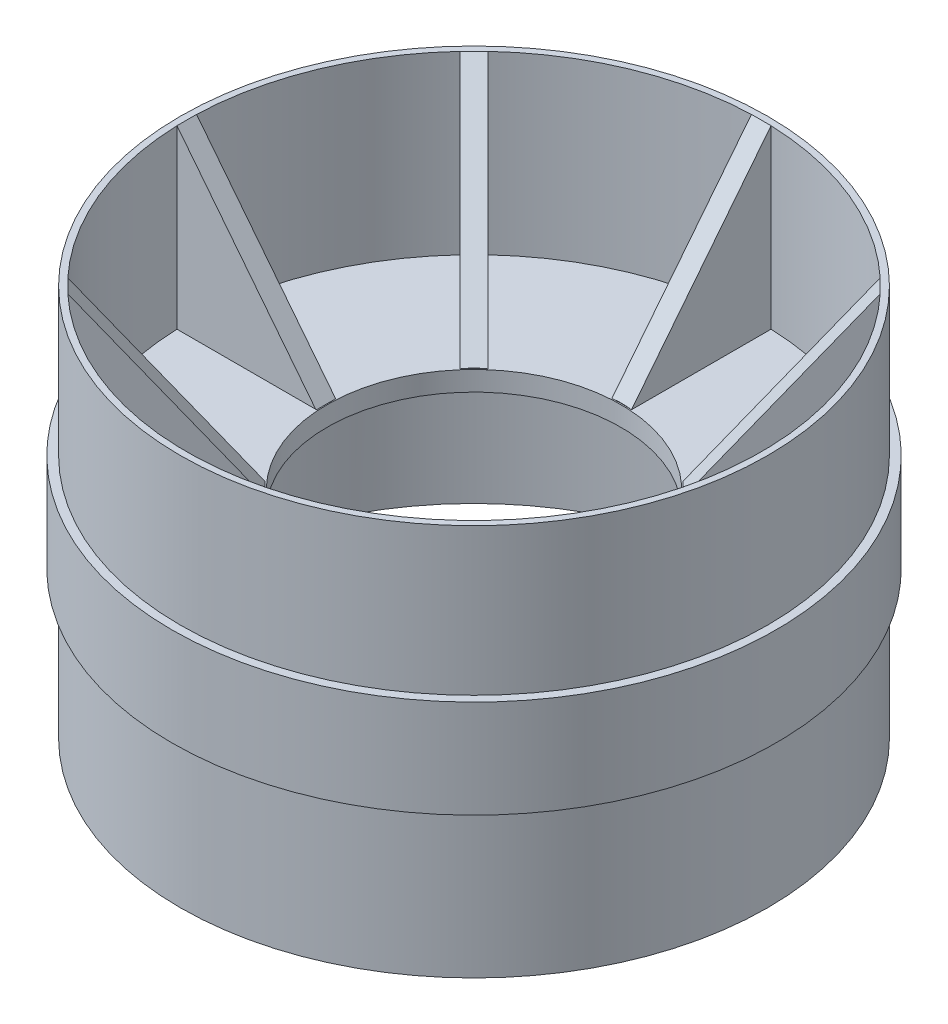
SolidWorks part; units mm, degrees
ref_plane "Front Plane" through (0, 0, 0) normal (0, 0, 1) x (1, 0, 0)
ref_plane "Top Plane" through (0, 0, 0) normal (0, 1, 0) x (1, 0, 0)
ref_plane "Right Plane" through (0, 0, 0) normal (1, 0, 0) x (0, 0, -1)
sketch "Sketch1" plane through (0, 0, 0) normal (0, 1, 0) x (1, 0, 0)
  circle A0 centre (0, 0) radius 74.549
  circle A1 centre (0, 0) radius 78.359
  dimension "D1" = 149.098
  dimension "D2" = 156.718
extrude "Boss-Extrude1" add sketch "Sketch1" along normal blind 25.4
sketch "Sketch2" plane through (0, 25.4, 0) normal (0, 1, 0) x (1, 0, 0)
  circle A0 centre (0, 0) radius 76.2
  circle A1 centre (0, 0) radius 74.549
extrude "Boss-Extrude2" add sketch "Sketch2" along normal blind 38.1
sketch "Sketch3" plane through (0, 0, 0) normal (0, -1, 0) x (1, 0, 0)
  circle A0 centre (0, 0) radius 76.2
  circle A1 centre (0, 0) radius 74.549
  dimension "D1" = 152.4
extrude "Boss-Extrude3" add sketch "Sketch3" along normal blind 38.1
ref_plane "Plane1" through (0, 12.7, 0) normal (0, 1, 0) x (1, 0, 0)
sketch "Sketch4" plane through (0, 12.7, 0) normal (0, 1, 0) x (1, 0, 0)
  circle A0 centre (0, 0) radius 74.549
  circle A1 centre (0, 0) radius 38.1
  dimension "D1" = 76.2
extrude "Boss-Extrude4" add sketch "Sketch4" along normal blind 5.08
sketch "Sketch5" plane through (0, 17.78, 0) normal (0, 1, 0) x (1, 0, 0)
  line L0 (38.3085, 2.54) -> (74.5057, 2.54)
  line L2 (74.5057, -2.54) -> (38.3085, -2.54)
  line L3 (34.8136, 0) -> (44.1618, 0) construction
  line L5 (28.8843, -25.2922) -> (54.4795, -50.8874)
  line L6 (50.8874, -54.4795) -> (25.2922, -28.8843)
  line L7 (2.54, -38.3085) -> (2.54, -74.5057)
  line L8 (-2.54, -74.5057) -> (-2.54, -38.3085)
  line L9 (-25.2922, -28.8843) -> (-50.8874, -54.4795)
  line L10 (-54.4795, -50.8874) -> (-28.8843, -25.2922)
  line L11 (-38.3085, -2.54) -> (-74.5057, -2.54)
  line L12 (-74.5057, 2.54) -> (-38.3085, 2.54)
  line L13 (-28.8843, 25.2922) -> (-54.4795, 50.8874)
  line L14 (-50.8874, 54.4795) -> (-25.2922, 28.8843)
  line L15 (-2.54, 38.3085) -> (-2.54, 74.5057)
  line L16 (2.54, 74.5057) -> (2.54, 38.3085)
  line L17 (25.2922, 28.8843) -> (50.8874, 54.4795)
  line L18 (54.4795, 50.8874) -> (28.8843, 25.2922)
  arc A2 (74.5057, 2.54) -> (74.5057, -2.54) centre (0, 0) cw
  circle A3 centre (0, 0) radius 74.549 construction
  arc A4 (38.3085, 2.54) -> (38.3085, -2.54) centre (0, 0) cw
  arc A5 (54.4795, -50.8874) -> (50.8874, -54.4795) centre (0, 0) cw
  arc A6 (28.8843, -25.2922) -> (25.2922, -28.8843) centre (0, 0) cw
  arc A7 (2.54, -74.5057) -> (-2.54, -74.5057) centre (0, 0) cw
  arc A8 (2.54, -38.3085) -> (-2.54, -38.3085) centre (0, 0) cw
  arc A9 (-50.8874, -54.4795) -> (-54.4795, -50.8874) centre (0, 0) cw
  arc A10 (-25.2922, -28.8843) -> (-28.8843, -25.2922) centre (0, 0) cw
  arc A11 (-74.5057, -2.54) -> (-74.5057, 2.54) centre (0, 0) cw
  arc A12 (-38.3085, -2.54) -> (-38.3085, 2.54) centre (0, 0) cw
  arc A13 (-54.4795, 50.8874) -> (-50.8874, 54.4795) centre (0, 0) cw
  arc A14 (-28.8843, 25.2922) -> (-25.2922, 28.8843) centre (0, 0) cw
  arc A15 (-2.54, 74.5057) -> (2.54, 74.5057) centre (0, 0) cw
  arc A16 (-2.54, 38.3085) -> (2.54, 38.3085) centre (0, 0) cw
  arc A17 (50.8874, 54.4795) -> (54.4795, 50.8874) centre (0, 0) cw
  arc A18 (25.2922, 28.8843) -> (28.8843, 25.2922) centre (0, 0) cw
  point P40 (0, 0)
  dimension "D1" = 2.54
  dimension "D2" = 2.54
  dimension "D3" = 8
extrude "Boss-Extrude10" add sketch "Sketch5" along normal blind 45.72
sketch "Sketch6" plane through (0, 0, 2.54) normal (0, 0, 1) x (1, 0, 0)
  line L0 (74.5057, 63.5) -> (38.3085, 17.78)
  line L1 (38.3085, 17.78) -> (38.3085, 63.5)
  line L2 (38.3085, 63.5) -> (74.5057, 63.5)
extrude "Cut-Extrude1" cut sketch "Sketch6" against normal blind 5.08
sketch "Sketch7" plane through (1.7961, 0, 1.7961) normal (0.7071, 0, 0.7071) x (0.7071, 0, -0.7071)
  line L0 (74.5057, 63.5) -> (38.3085, 17.78)
  line L1 (38.3085, 17.78) -> (38.3085, 63.5)
  line L2 (38.3085, 63.5) -> (74.5057, 63.5)
extrude "Cut-Extrude2" cut sketch "Sketch7" against normal blind 5.08
sketch "Sketch8" plane through (2.54, 0, 0) normal (1, 0, 0) x (0, 0, -1)
  line L0 (74.5057, 63.5) -> (38.3085, 17.78)
  line L1 (38.3085, 17.78) -> (38.3085, 63.5)
  line L2 (38.3085, 63.5) -> (74.5057, 63.5)
extrude "Cut-Extrude3" cut sketch "Sketch8" against normal blind 5.08
sketch "Sketch9" plane through (-1.7961, 0, 1.7961) normal (-0.7071, 0, 0.7071) x (0.7071, 0, 0.7071)
  line L0 (-74.5057, 63.5) -> (-38.3085, 17.78)
  line L1 (-38.3085, 17.78) -> (-38.3085, 63.5)
  line L2 (-38.3085, 63.5) -> (-74.5057, 63.5)
extrude "Cut-Extrude4" cut sketch "Sketch9" against normal blind 5.08
sketch "Sketch10" plane through (0, 0, 2.54) normal (0, 0, 1) x (1, 0, 0)
  line L0 (-74.5057, 63.5) -> (-38.3085, 17.5103)
  line L1 (-38.3085, 17.5103) -> (-38.3085, 63.5)
  line L2 (-38.3085, 63.5) -> (-74.5057, 63.5)
extrude "Cut-Extrude5" cut sketch "Sketch10" against normal blind 5.08
sketch "Sketch11" plane through (1.7961, 0, 1.7961) normal (0.7071, 0, 0.7071) x (0.7071, 0, -0.7071)
  line L0 (-74.5057, 63.5) -> (-38.3085, 17.78)
  line L1 (-38.3085, 17.78) -> (-38.3085, 63.5)
  line L2 (-38.3085, 63.5) -> (-74.5057, 63.5)
extrude "Cut-Extrude6" cut sketch "Sketch11" against normal blind 5.08
sketch "Sketch12" plane through (-2.54, 0, 0) normal (-1, 0, 0) x (0, 0, 1)
  line L0 (74.5057, 63.5) -> (38.3085, 17.78)
  line L1 (38.3085, 17.78) -> (38.3085, 63.5)
  line L2 (38.3085, 63.5) -> (74.5057, 63.5)
extrude "Cut-Extrude7" cut sketch "Sketch12" against normal blind 5.08
sketch "Sketch13" plane through (-1.7961, 0, 1.7961) normal (-0.7071, 0, 0.7071) x (0.7071, 0, 0.7071)
  line L0 (74.5057, 63.5) -> (38.3085, 17.78)
  line L1 (38.3085, 17.78) -> (38.3085, 63.5)
  line L2 (38.3085, 63.5) -> (74.5057, 63.5)
extrude "Cut-Extrude8" cut sketch "Sketch13" against normal blind 5.08
